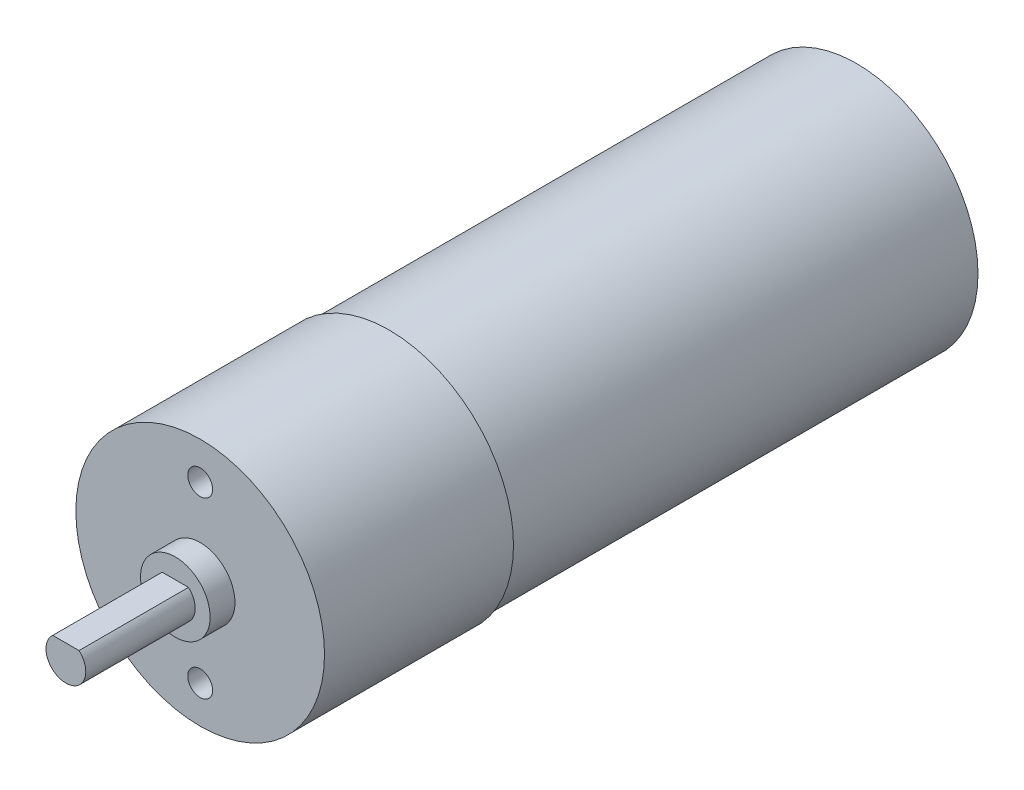
SolidWorks part; units mm, degrees
ref_plane "Front Plane" through (0, 0, 0) normal (0, 0, 1) x (1, 0, 0)
ref_plane "Top Plane" through (0, 0, 0) normal (0, 1, 0) x (1, 0, 0)
ref_plane "Right Plane" through (0, 0, 0) normal (1, 0, 0) x (0, 0, -1)
sketch "Sketch1" plane through (0, 0, 0) normal (0, 0, 1) x (1, 0, 0)
  circle A0 centre (0, 0) radius 12.2
  circle A1 centre (0, 0) radius 12.5
  dimension "D1" = 24.4
  dimension "D2" = 25
extrude "Boss-Extrude1" add sketch "Sketch1" along normal blind 47 contours A0 region at (0, 0, 0)
extrude "Boss-Extrude2" add sketch "Sketch1<3>" along normal blind 19 from surface contours A0 | A1 A0 region at (0, 0, 0) region at (-12.4646, 0, 0) starting at face at (12.2, 0, 47)
sketch "Sketch1<3>" plane through (0, 0, 0) normal (0, 0, 1) x (1, 0, 0) same geometry as "Sketch1"
sketch "Sketch2" plane through (0, 0, 66) normal (0, 0, 1) x (1, 0, 0)
  line L0 (-1.3229, 1.5) -> (1.3229, 1.5)
  circle A0 centre (0, 0) radius 3.5
  circle A1 centre (0, 0) radius 2
  dimension "D1" = 7
  dimension "D2" = 4
  dimension "D3" = 0.5
extrude "Boss-Extrude4" add sketch "Sketch2" along normal blind 2.5 contours L0 A1 | L0 A1 | A0 A1 region at (0, 1.7023, 66) region at (0, -0.1324, 66) region at (-3.401, 0, 66)
extrude "Boss-Extrude5" add sketch "Sketch2<4>" along normal blind 11 from surface contours L0 A1 region at (0, -0.1324, 66) starting at face at (3.5, 0, 68.5)
sketch "Sketch2<4>" plane through (0, 0, 66) normal (0, 0, 1) x (1, 0, 0) same geometry as "Sketch2"
sketch "Sketch3" plane through (0, 0, 66) normal (0, 0, 1) x (1, 0, 0)
  line L0 (0, 12.5) -> (0, -12.5) construction
  line L1 (-12.5, 0) -> (12.5, 0) construction
  circle A0 centre (0, 0) radius 12.5 construction
  circle A2 centre (0, 8.75) radius 1.5
  circle A3 centre (0, -8.75) radius 1.5
  dimension "D1" = 3
  dimension "D2" = 14.5
hole_wizard "M3x0.5 Tapped Hole1" positions "3DSketch1" profile "Sketch4" tap size "M3x0.5" standard "ANSI Metric"
sketch3d "3DSketch1"
  point P0 (0, 8.75, 66)
  point P6 (0, -8.75, 66)
sketch "Sketch4" plane through (0, 8.75, 66) normal (1, 0, 0) x (0, -1, 0)
  line L0 (0, 0) -> (0, 20.7511)
  line L1 (0, 20.7511) -> (1.25, 20)
  line L2 (1.25, 20) -> (1.25, 0)
  line L5 (1.25, 0) -> (0, 0)
  line L10 (0, 20.7511) -> (-1.25, 20) construction
  line L11 (0, -6.35) -> (0, 107.95) construction
  dimension "Tap Drill Dia." = 2.5
  dimension "Tap Drill Depth" = 20
  dimension "Drill Angle" = 118
